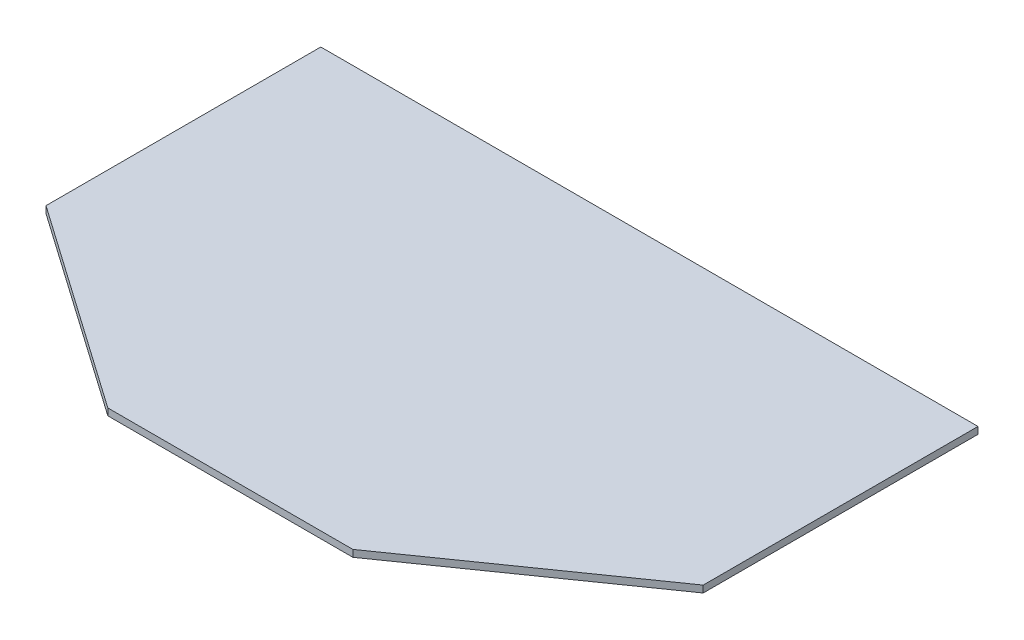
SolidWorks part; units mm, degrees
material "Acrílico (Impacto medio-alto)"
ref_plane "Alzado" through (0, 0, 0) normal (0, 0, 1) x (1, 0, 0)
ref_plane "Planta" through (0, 0, 0) normal (0, 1, 0) x (1, 0, 0)
ref_plane "Vista lateral" through (0, 0, 0) normal (1, 0, 0) x (0, 0, -1)
sketch "Sketch1" plane through (0, 0, 0) normal (0, 1, 0) x (1, 0, 0)
  line L0 (-143.5, -60) -> (-53.5, -123)
  line L1 (-143.5, -60) -> (143.5, -60) construction
  line L2 (-143.5, -60) -> (-143.5, 60)
  line L3 (-143.5, 60) -> (143.5, 60)
  line L4 (143.5, -60) -> (143.5, 60)
  line L5 (-143.5, -60) -> (143.5, 60) construction
  line L6 (-143.5, 60) -> (143.5, -60) construction
  line L7 (-53.5, -123) -> (53.5, -123)
  line L8 (53.5, -123) -> (143.5, -60)
  point P0 (0, 0)
  point P6 (0, -123)
  point P9 (0, -60)
  dimension "D1" = 120
  dimension "D2" = 287
  dimension "D3" = 63
  dimension "D4" = 107
extrude "Boss-Extrude1" add sketch "Sketch1" along normal blind 3
